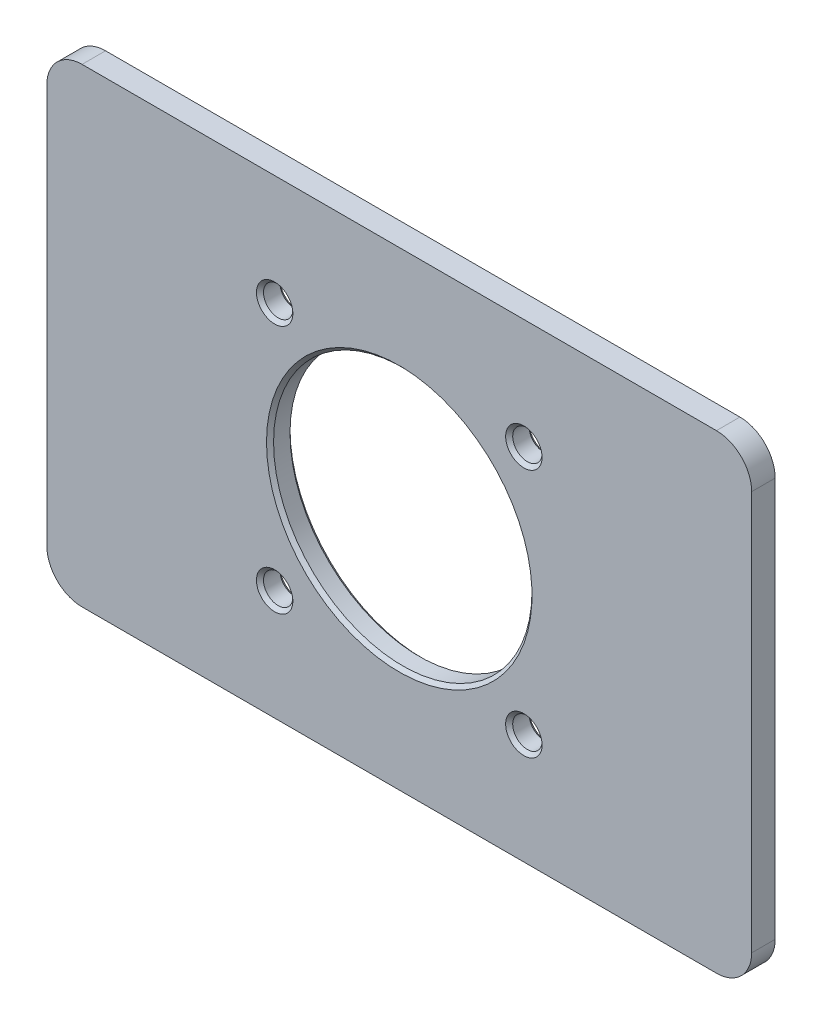
SolidWorks part; units mm, degrees
ref_plane "Płaszczyzna przednia" through (0, 0, 0) normal (0, 0, 1) x (1, 0, 0)
ref_plane "Płaszczyzna górna" through (0, 0, 0) normal (0, 1, 0) x (1, 0, 0)
ref_plane "Płaszczyzna prawa" through (0, 0, 0) normal (1, 0, 0) x (0, 0, -1)
sketch "Szkic1" plane through (0, 0, 0) normal (0, 0, 1) x (1, 0, 0)
  line L0 (0, 0) -> (-23.297, 23.297) construction
  line L1 (-27, -20) -> (27, -20)
  line L2 (-30, -17) -> (-30, 17)
  line L3 (-27, 20) -> (27, 20)
  line L4 (30, -17) -> (30, 17)
  line L5 (-30, -20) -> (30, 20) construction
  line L6 (-30, 20) -> (30, -20) construction
  line L7 (0, 0) -> (25.2349, 25.2349) construction
  arc A0 (27, 20) -> (30, 17) centre (27, 17) cw
  arc A1 (27, -20) -> (30, -17) centre (27, -17) ccw
  arc A2 (-27, -20) -> (-30, -17) centre (-27, -17) cw
  arc A3 (-30, 17) -> (-27, 20) centre (-27, 17) cw
  circle A4 centre (0, 0) radius 11
  circle A8 centre (-10.6066, -10.6066) radius 1.25
  circle A9 centre (10.6066, -10.6066) radius 1.25
  circle A10 centre (10.6066, 10.6066) radius 1.25
  circle A11 centre (-10.6066, 10.6066) radius 1.25
  circle A12 centre (0, 0) radius 15 construction
  point P0 (0, 0)
  dimension "D3" = 3
  dimension "D4" = 30
  dimension "D6" = 2.5
  dimension "D7" = 2.5
  dimension "D8" = 2.5
  dimension "D9" = 2.5
  dimension "D10" = 22
  dimension "D1" = 60
  dimension "D2" = 40
  dimension "D5" = 45
extrude "Dodanie-wyciągnięcie1" add sketch "Szkic1" along normal blind 2
chamfer "Sfazowanie1" distance 0.3 angle 45 10 edges at (11.8566, 10.6066, 0) (-9.3566, 10.6066, 0) (11, 0, 0) (-9.3566, -10.6066, 0) (11.8566, -10.6066, 0) (-9.3566, -10.6066, 2) (11.8566, -10.6066, 2) (11.8566, 10.6066, 2) (-9.3566, 10.6066, 2) (11, 0, 2)
equation "\"D7@Szkic1\"=\"D6@Szkic1\""
equation "\"D8@Szkic1\"=\"D6@Szkic1\""
equation "\"D9@Szkic1\"=\"D6@Szkic1\""
